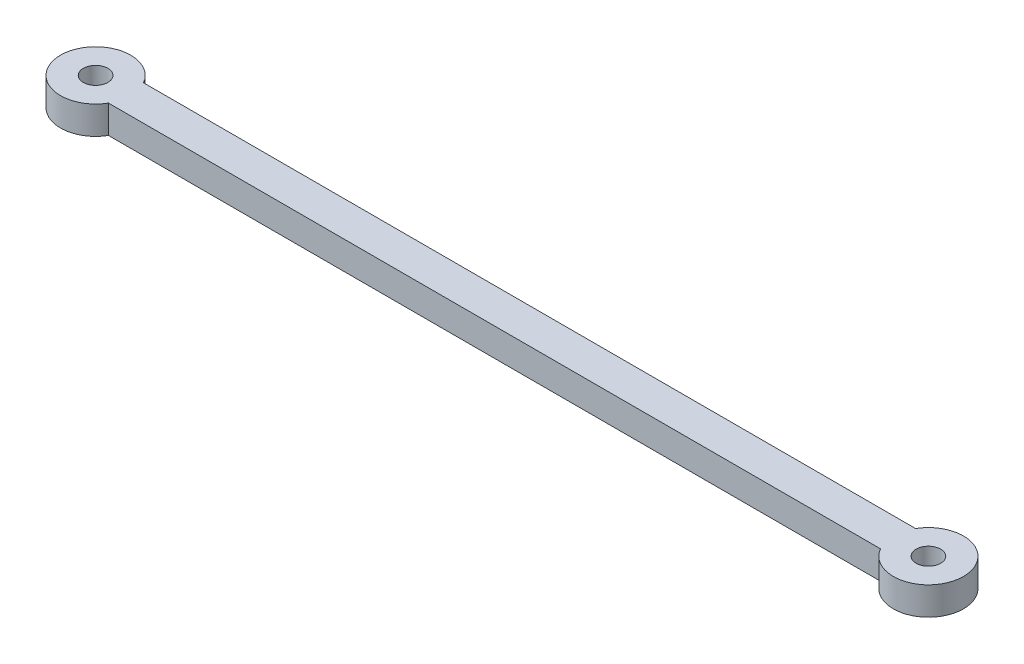
SolidWorks part; units mm, degrees
ref_plane "Front Plane" through (0, 0, 0) normal (0, 0, 1) x (1, 0, 0)
ref_plane "Top Plane" through (0, 0, 0) normal (0, 1, 0) x (1, 0, 0)
ref_plane "Right Plane" through (0, 0, 0) normal (1, 0, 0) x (0, 0, -1)
sketch "Sketch1" plane through (0, 0, 0) normal (0, 1, 0) x (1, 0, 0)
  line L0 (-55, 2.5) -> (55, 2.5)
  line L1 (-55, -2.5) -> (55, -2.5)
  line L2 (-55, 0) -> (55, 0) construction
  arc A1 (-55, 2.5) -> (-55, -2.5) centre (-59.3301, 0) ccw
  arc A2 (55, 2.5) -> (55, -2.5) centre (59.3301, 0) cw
  dimension "D2" = 55
  dimension "D3" = 5
  dimension "D7" = 5
  dimension "D1" = 5
  dimension "D4" = 110
  dimension "D5" = 110
  dimension "D6" = 2.5
extrude "Boss-Extrude1" add sketch "Sketch1" along normal blind 4
sketch "Sketch2" plane through (0, 4, 0) normal (0, 1, 0) x (1, 0, 0)
  circle A0 centre (-59.3301, 0) radius 1.75
  circle A1 centre (59.3301, 0) radius 1.75
  dimension "D1" = 3.5
  dimension "D2" = 3.5
extrude "Cut-Extrude1" cut sketch "Sketch2" against normal through all
